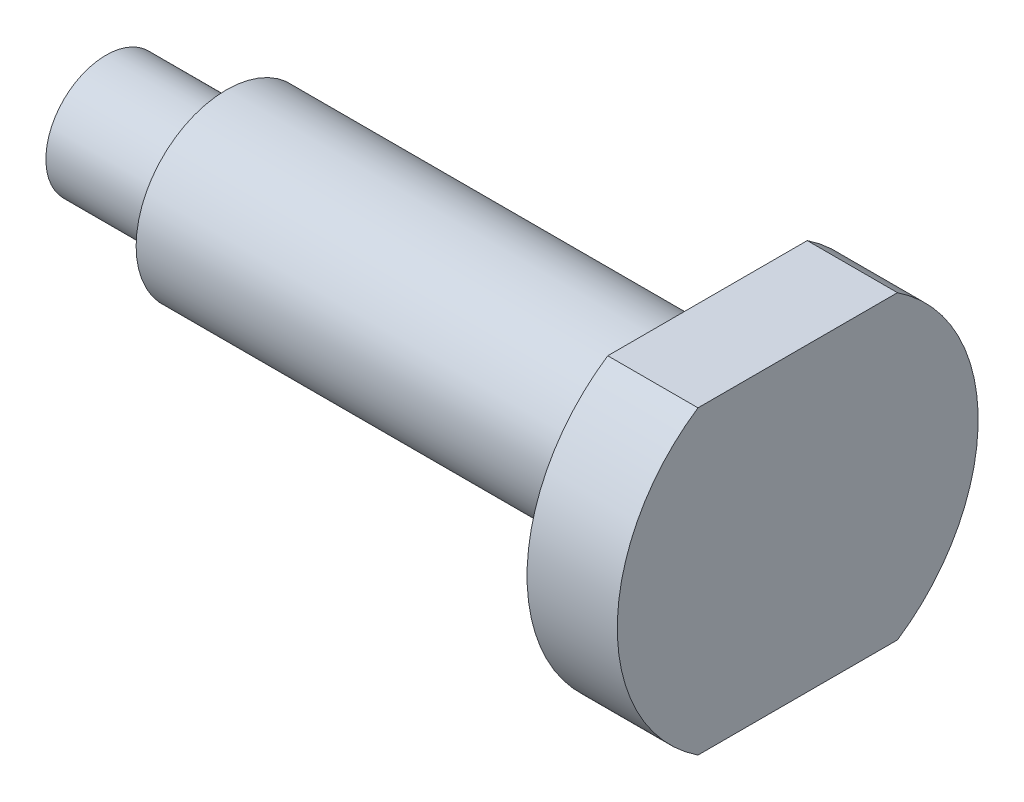
SolidWorks part; units mm, degrees
material "201 Annealed Stainless Steel (SS)"
ref_plane "Front Plane" through (0, 0, 0) normal (0, 0, 1) x (1, 0, 0)
ref_plane "Top Plane" through (0, 0, 0) normal (0, 1, 0) x (1, 0, 0)
ref_plane "Right Plane" through (0, 0, 0) normal (1, 0, 0) x (0, 0, -1)
sketch "Sketch2" plane through (0, 0, 0) normal (1, 0, 0) x (0, 0, -1)
  line L0 (-3.3166, 5) -> (3.3166, 5)
  line L1 (0, 0) -> (-50000, 0) construction
  line L2 (-3.3166, -5) -> (3.3166, -5)
  arc A0 (-3.3166, 5) -> (-3.3166, -5) centre (0, 0) ccw
  circle A1 centre (0, 0) radius 3
  circle A2 centre (0, 0) radius 2
  arc A3 (3.3166, -5) -> (3.3166, 5) centre (0, 0) ccw
  dimension "D1" = 12
  dimension "D2" = 6
  dimension "D3" = 4
  dimension "D4" = 10
extrude "Boss-Extrude1" add sketch "Sketch2" along normal blind 3 contours L1 A3 L0 A0 A1 | A3 L1 A1 A0 L2 | A1 L1 A2 | L1 A1 A2 | A2 L1 | L0 A3 L2 A0 region at (0, 1.9434, 0) region at (0, 2.9151, 0) region at (0, 4.8438, 0)
extrude "Boss-Extrude2" add sketch "Sketch2<4>" against normal blind 16 contours L1 A1 A2 | A1 L1 A2 region at (0, 2.9151, 0)
sketch "Sketch2<4>" plane through (0, 0, 0) normal (1, 0, 0) x (0, 0, -1) same geometry as "Sketch2"
extrude "Boss-Extrude3" add sketch "Sketch2<5>" against normal blind 20 contours A2 L1 | L1 A2 region at (0, 1.9434, 0)
sketch "Sketch2<5>" plane through (0, 0, 0) normal (1, 0, 0) x (0, 0, -1) same geometry as "Sketch2"
cosmetic thread "Cosmetic Thread1" parameters "D2"=3.22
